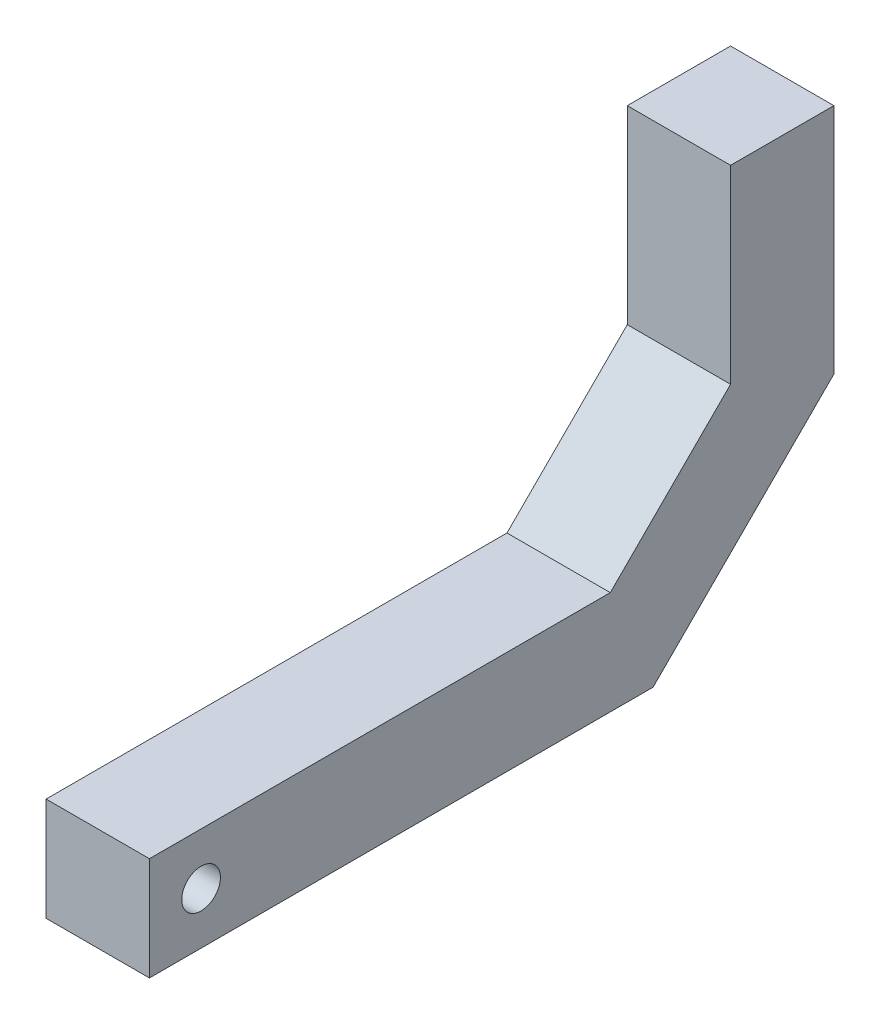
SolidWorks part; units mm, degrees
ref_plane "Front Plane" through (0, 0, 0) normal (0, 0, 1) x (1, 0, 0)
ref_plane "Top Plane" through (0, 0, 0) normal (0, 1, 0) x (1, 0, 0)
ref_plane "Right Plane" through (0, 0, 0) normal (1, 0, 0) x (0, 0, -1)
ref_axis "Z" through (0, 0, 55.65) along (0, 0, -1)
sketch "Sketch1" plane through (0, 0, 0) normal (1, 0, 0) x (0, 0, -1)
  line L0 (-8, 4) -> (0, 4)
  line L1 (0, 4) -> (0, -14)
  line L2 (0, -14) -> (-14, -28)
  line L3 (-14, -28) -> (-45, -28)
  line L4 (-45, -28) -> (-45, -20) construction
  line L5 (-45, -20) -> (-17.3137, -20)
  line L6 (-17.3137, -20) -> (-8, -10.6863)
  line L7 (-8, -10.6863) -> (-8, 4)
  line L8 (-13.4134, -16.0997) -> (-7.7566, -21.7566) construction
  line L9 (-49, -20) -> (-49, -28) construction
  line L10 (-45, -20) -> (-53, -20)
  line L11 (-45, -20) -> (-45, -28) construction
  line L12 (-45, -28) -> (-53, -28)
  line L13 (-53, -20) -> (-53, -28)
  circle A0 centre (-49, -24) radius 1.5
  point P17 (-50.5599, -30.0678)
  point P18 (0, 0)
  point P19 (0, 0)
  point P20 (-49, -24)
  dimension "D8" = 3
  dimension "D1" = 8
  dimension "D2" = 45
  dimension "D3" = 28
  dimension "D4" = 4
  dimension "D5" = 135
  dimension "D6" = 14
  dimension "D7" = 8
extrude "Boss-Extrude1" add sketch "Sketch1" along normal blind 4 and the other way blind 4
equation "\"rbracket-width\"= 8"
equation "\"D1@Boss-Extrude1\"=\"rbracket-width\"/2"
equation "\"D2@Boss-Extrude1\"=\"rbracket-width\"/2"
equation "\"EyeCaptureRadius\"= ( \"EyeDiameter\" + \"EyeClearance\" ) / 2"
equation "\"rbracket_planetocenterline_dist\"= \"BasePlaneDistance\""
equation "\"D2@Sketch1\"=\"rbracket_planetocenterline_dist\""
equation "\"EyeDiameter\" = 28"
equation "\"BasePlaneDistance\" = 45"
equation "\"EyeClearance\" = 2"
equation "\"D1@Sketch1\"=\"rbracket-width\""
equation "\"D3@Sketch1\"=\"EyeDiameter\""
equation "\"D4@Sketch1\"=\"rbracket-width\"/2"
equation "\"D6@Sketch1\"=\"EyeDiameter\"/2"
equation "\"D7@Sketch1\"=\"rbracket-width\""
